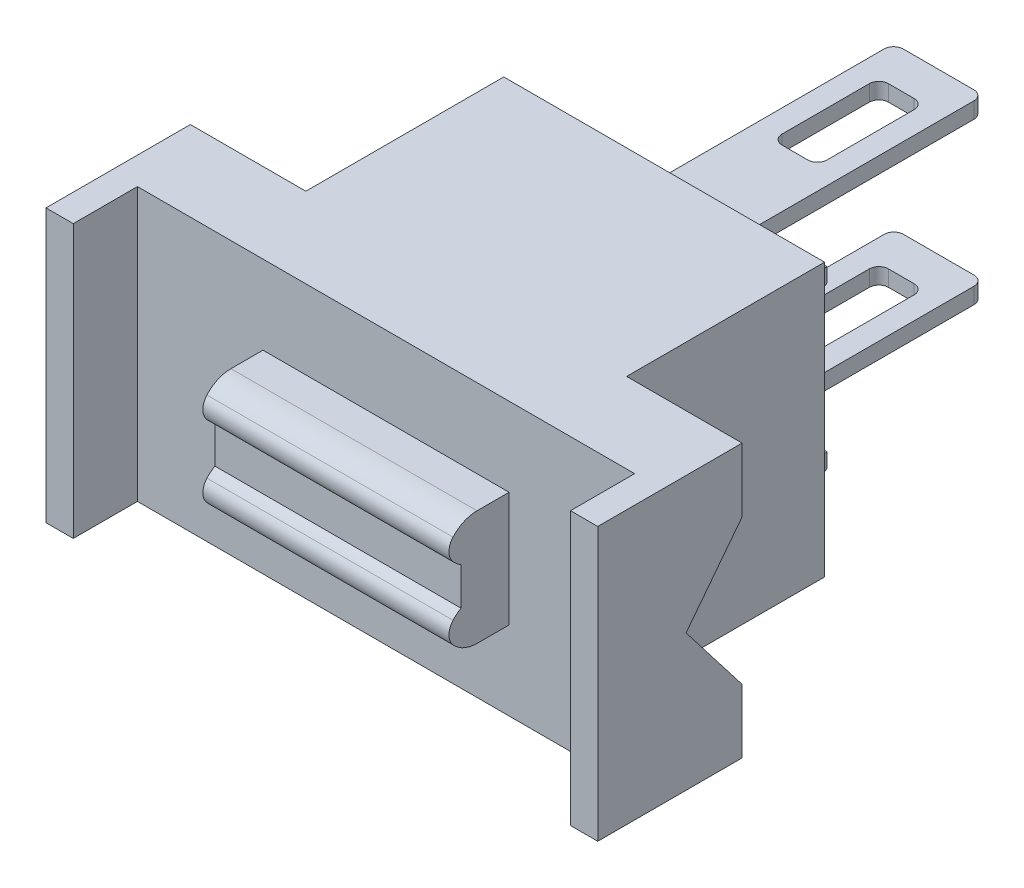
SolidWorks part; units mm, degrees
ref_plane "Front Plane" through (0, 0, 0) normal (0, 0, 1) x (1, 0, 0)
ref_plane "Top Plane" through (0, 0, 0) normal (0, 1, 0) x (1, 0, 0)
ref_plane "Right Plane" through (0, 0, 0) normal (1, 0, 0) x (0, 0, -1)
sketch "Sketch1" plane through (0, 0, 0) normal (0, 0, 1) x (1, 0, 0)
  line L1 (-5, 4.25) -> (5, 4.25)
  line L2 (-5, 4.25) -> (-5, -4.25)
  line L3 (-5, -4.25) -> (5, -4.25)
  line L4 (5, 4.25) -> (5, -4.25)
  line L5 (-5, 4.25) -> (5, -4.25) construction
  line L6 (-5, -4.25) -> (5, 4.25) construction
  point P0 (0, 0)
  dimension "D1" = 8.5
  dimension "D2" = 10
extrude "Boss-Extrude1" add sketch "Sketch1" along normal blind 10.67
sketch "Sketch2" plane through (0, 0, 0) normal (0, 0, -1) x (-1, 0, 0)
  line L1 (-3.578, -2.3287) -> (3.822, -2.3287)
  line L2 (-3.578, -2.3287) -> (-3.578, -2.8287)
  line L3 (-3.578, -2.8287) -> (3.822, -2.8287)
  line L4 (3.822, -2.3287) -> (3.822, -2.8287)
  line L5 (3.822, 2.1713) -> (-3.578, 2.1713)
  line L6 (3.822, 2.1713) -> (3.822, 2.6713)
  line L7 (3.822, 2.6713) -> (-3.578, 2.6713)
  line L8 (-3.578, 2.1713) -> (-3.578, 2.6713)
  point P12 (0.2962, 3.7)
  point P13 (-7.3784, -3.7)
  dimension "D1" = 7.4
  dimension "D2" = 7.4
  dimension "D3" = 0.5
  dimension "D4" = 4.5
  dimension "D5" = 0.5
extrude "Boss-Extrude2" add sketch "Sketch2" along normal blind 1.5
sketch "Sketch3" plane through (0, 0, -1.5) normal (0, 0, -1) x (-1, 0, 0)
  line L0 (0, 0) -> (0, -2.3287) construction
  line L1 (3.822, -2.3287) -> (-3.578, -2.3287) construction
  line L8 (-1.4, -2.3287) -> (1.4, -2.3287)
  line L9 (-1.4, -2.3287) -> (-1.4, -2.8287)
  line L10 (-1.4, -2.8287) -> (1.4, -2.8287)
  line L11 (1.4, -2.3287) -> (1.4, -2.8287)
  line L12 (-3.578, -2.8287) -> (3.822, -2.8287) construction
  line L13 (3.822, 2.6713) -> (-3.578, 2.6713) construction
  line L14 (-1.3936, 2.6713) -> (1.4064, 2.6713)
  line L15 (-1.3936, 2.6713) -> (-1.3936, 2.1713)
  line L16 (-1.3936, 2.1713) -> (1.4064, 2.1713)
  line L17 (1.4064, 2.6713) -> (1.4064, 2.1713)
  line L18 (-3.578, 2.1713) -> (3.822, 2.1713) construction
  point P4 (0, 0)
  point P5 (0, 0)
  point P9 (0, -2.3287)
  dimension "D2" = 2.8
extrude "Boss-Extrude3" add sketch "Sketch3" along normal blind 7.06
fillet "Fillet4" radius 0.1 4 edges at (2.489, -2.8287, -1.5) (2.4858, 2.1713, -1.5) (-2.6142, 2.6713, -1.5) (-2.611, -2.3287, -1.5)
sketch "Sketch5" plane through (5, 0, 0) normal (1, 0, 0) x (0, 0, -1)
  line L0 (-10.67, 4.25) -> (0, 4.25) construction
  line L1 (-10.67, -4.25) -> (-6.17, -4.25)
  line L2 (-10.67, -4.25) -> (-10.67, 4.25)
  line L3 (-10.67, 4.25) -> (-6.17, 4.25)
  line L4 (-6.17, -4.25) -> (-6.17, 4.25)
  dimension "D1" = 4.5
extrude "Boss-Extrude4" add sketch "Sketch5" along normal blind 3.6
sketch "Sketch6" plane through (-5, 0, 0) normal (-1, 0, 0) x (0, 0, 1)
  line L0 (10.67, 4.25) -> (0, 4.25) construction
  line L1 (10.67, -4.25) -> (6.17, -4.25)
  line L2 (10.67, -4.25) -> (10.67, 4.25)
  line L3 (10.67, 4.25) -> (6.17, 4.25)
  line L4 (6.17, -4.25) -> (6.17, 4.25)
  dimension "D1" = 4.5
extrude "Boss-Extrude5" add sketch "Sketch6" along normal blind 3.6
sketch "Sketch7" plane through (8.6, 0, 0) normal (1, 0, 0) x (0, 0, -1)
  line L0 (-6.17, -4.25) -> (-6.17, 4.25) construction
  line L1 (-7.92, 0.004) -> (-6.17, -2.2629)
  line L2 (-6.0334, -2.4487) -> (-6.0569, 2.4034)
  line L3 (-7.92, -0.004) -> (-6.0569, 2.4034)
  line L4 (-10.67, 4.25) -> (-10.67, -4.25) construction
  arc A0 (-6.17, -2.2629) -> (-6.0334, -2.4487) centre (-10.0706, -5.274) cw
  line M6 (-6.17, -4.25) -> (-6.17, 4.25)
  dimension "D1" = 2.75
  dimension "D2" = 2.75
extrude "Cut-Extrude2" cut sketch "Sketch7" against normal up to surface (13.6 mm away) contours L3 L1 M6
mirror "Mirror2" about plane through (0, 0, 0) normal (1, 0, 0) of "Cut-Extrude2"
sketch "Sketch8" plane through (5, 0, 0) normal (1, 0, 0) x (0, 0, -1)
  line L0 (-6.17, -2.2629) -> (-7.9169, 0)
  line L1 (-7.9169, 0) -> (-6.17, -2.2629) construction
  line L2 (-7.9169, 0) -> (-6.17, 2.2573)
  line L3 (-6.17, 2.2573) -> (-6.17, -2.2629)
extrude "Boss-Extrude6" add sketch "Sketch8" against normal up to surface (10 mm away) up to face at (-5, -0.0009, 4.1133)
sketch "Sketch9" plane through (0, 0, 10.67) normal (0, 0, 1) x (1, 0, 0)
  line L0 (-8.6, -4.25) -> (8.6, -4.25) construction
  line L4 (-7.75, 4.25) -> (-7.75, -4.25)
  line L5 (-7.75, 4.25) -> (7.75, 4.25)
  line L9 (7.75, 4.25) -> (7.75, -4.25)
  line L14 (7.75, -4.25) -> (-7.75, -4.25)
extrude "Cut-Extrude3" cut sketch "Sketch9" against normal blind 2
sketch "Sketch10" plane through (0, 0, 8.67) normal (0, 0, 1) x (1, 0, 0)
  line L1 (-3.8359, 1.7907) -> (3.8359, 1.7907)
  line L2 (-3.8359, 1.7907) -> (-3.8359, -1.7907)
  line L3 (-3.8359, -1.7907) -> (3.8359, -1.7907)
  line L4 (3.8359, 1.7907) -> (3.8359, -1.7907)
  line L5 (-3.8359, 1.7907) -> (3.8359, -1.7907) construction
  line L6 (-3.8359, -1.7907) -> (3.8359, 1.7907) construction
  point P0 (0, 0)
extrude "Boss-Extrude7" add sketch "Sketch10" along normal blind 2
sketch "Sketch12" plane through (0, 0, 10.67) normal (0, 0, 1) x (1, 0, 0)
  line L0 (-3.8359, 1.7907) -> (-3.8359, -1.7907) construction
  line L1 (3.8359, 0.5882) -> (-3.8359, 0.5882)
  line L2 (3.8359, 0.5882) -> (3.8359, -0.5882)
  line L3 (3.8359, -0.5882) -> (-3.8359, -0.5882)
  line L4 (-3.8359, 0.5882) -> (-3.8359, -0.5882)
  line L5 (3.8359, 0.5882) -> (-3.8359, -0.5882) construction
  line L6 (3.8359, -0.5882) -> (-3.8359, 0.5882) construction
  point P0 (0, 0)
extrude "Cut-Extrude4" cut sketch "Sketch12" against normal blind 0.5
fillet "Fillet7" radius 1 4 edges at (0, 0.5882, 10.67) (0, -0.5882, 10.67) (0, -1.7907, 10.67) (0, 1.7907, 10.67)
fillet "Fillet8" radius 0.5 2 edges at (0, 1.1224, 10.6134) (0, -1.1224, 10.6134)
sketch "Sketch13" plane through (0, 2.6713, 0) normal (0, 1, 0) x (1, 0, 0)
  line L0 (1.4, 8.56) -> (1.4, 1.5) construction
  line L1 (0.7, 7.3938) -> (-0.7, 7.3938)
  line L2 (0.7, 7.3938) -> (0.7, 4.0762)
  line L3 (0.7, 4.0762) -> (-0.7, 4.0762)
  line L4 (-0.7, 7.3938) -> (-0.7, 4.0762)
  dimension "D1" = 0.7
  dimension "D2" = 1.4
extrude "Cut-Extrude5" cut sketch "Sketch13" against normal blind 10
fillet "Fillet9" radius 0.3 12 edges at (-0.7, -2.5787, -7.3938) (0.7, -2.5787, -7.3938) (1.4, -2.5787, -8.56) (-1.4, -2.5787, -8.56) (0.7, -2.5787, -4.0762) (-0.7, -2.5787, -4.0762) (-1.4064, 2.4213, -8.56) (1.3936, 2.4213, -8.56) (0.7, 2.4213, -4.0762) (-0.7, 2.4213, -7.3938) (0.7, 2.4213, -7.3938) (-0.7, 2.4213, -4.0762)
